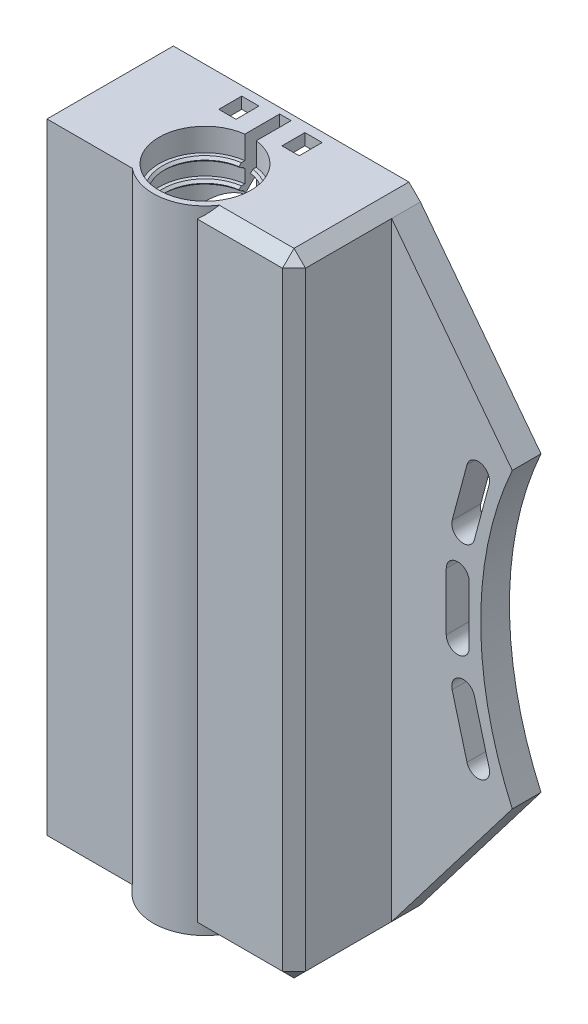
SolidWorks part; units mm, degrees
ref_plane "Alzado" through (0, 0, 0) normal (0, 0, 1) x (1, 0, 0)
ref_plane "Planta" through (0, 0, 0) normal (0, 1, 0) x (1, 0, 0)
ref_plane "Vista lateral" through (0, 0, 0) normal (1, 0, 0) x (0, 0, -1)
sketch "Croquis1" plane through (0, 0, 0) normal (0, 1, 0) x (1, 0, 0)
  line L1 (-5.6569, -7) -> (-22.5, -7)
  line L2 (-22.5, -7) -> (-22.5, 15)
  line L3 (-22.5, 15) -> (22.5, 15)
  line L4 (22.5, 15) -> (22.5, -7)
  line L5 (22.5, -7) -> (5.6569, -7)
  line L7 (0, 0) -> (0, 15696.111) construction
  line L8 (0, 0) -> (15696.111, 0) construction
  circle A0 centre (0, 0) radius 8
  arc A1 (-5.6569, -7) -> (5.6569, -7) centre (0, 0) ccw
  point P5 (0, 15)
  dimension "D1" = 16
  dimension "D2" = 9
  dimension "D3" = 45
  dimension "D4" = 22
  dimension "D5" = 15
extrude "Saliente-Extruir1" add sketch "Croquis1" along normal mid plane 110
sketch "Croquis3" plane through (0, 55, 0) normal (0, 1, 0) x (1, 0, 0)
  circle A0 centre (0, 0) radius 8
  circle A1 centre (0, 0) radius 7
  circle A2 centre (0, 0) radius 8 construction
  dimension "D1" = 1
extrude "Saliente-Extruir2" add sketch "Croquis3" against normal blind 0.8 from offset 4 offset against normal yes
pattern_linear "MatrizL1" count 2 spacing 3.5 along (0, -1, 0) of "Saliente-Extruir2"
mirror "Simetría1" about plane through (0, 0, 0) normal (0, 1, 0) of "MatrizL1"
chamfer "Chaflán3" distance 2 angle 45 9 edges at (-22.5, 55, -4) (-22.5, 0, 7) (-22.5, -55, -4) (-14.0784, -55, 7) (22.5, -55, -4) (22.5, 55, -4) (14.0784, -55, 7) (22.5, 0, 7) (14.0784, 55, 7)
shell "Vaciado1" thickness 2 removed face at (0, 0, -15)
sketch "Croquis6" plane through (0, 0, 0) normal (1, 0, 0) x (0, 0, -1)
  line L0 (15, 53) -> (-5, 33)
  line L1 (15, 53) -> (15, -53) construction
  line L3 (-5, 33) -> (-5, 0)
  line L4 (-5, 0) -> (15, 0)
  line L5 (15, 0) -> (15, 53)
  line L6 (15, 53) -> (-5, 53) construction
  line L7 (-5, 53) -> (-5, -53) construction
  dimension "D1" = 45
extrude "Cortar-Extruir4" cut sketch "Croquis6" against normal mid plane 25
mirror "Simetría2" about plane through (0, 0, 0) normal (0, 1, 0) of "Cortar-Extruir4"
chamfer "Chaflán1" distance 0.4 angle 45 8 edges at (0, 51, 7) (0, 50.2, 7) (0, 47.5, 7) (0, 46.7, 7) (0, -46.7, 7) (0, -47.5, 7) (0, -50.2, 7) (0, -51, 7)
chamfer "Chaflán2" distance 0.4 angle 45 4 edges at (0, 50.2, 8) (0, 46.7, 8) (0, -47.5, -8) (0, -51, -8)
sketch "Croquis4" plane through (0, 55, 0) normal (0, 1, 0) x (1, 0, 0)
  line L0 (0, 0) -> (0, 50000) construction
  line L2 (-1, 14) -> (1, 14)
  line L3 (-1, 14) -> (-1, 0)
  line L4 (-1, 0) -> (1, 0)
  line L5 (1, 14) -> (1, 0)
  line L6 (-1, 14) -> (1, 0) construction
  line L7 (-1, 0) -> (1, 14) construction
  line L9 (20.5, 15) -> (-20.5, 15) construction
  point P3 (0, 7)
  dimension "D1" = 2
  dimension "D2" = 1
extrude "Cortar-Extruir3" cut sketch "Croquis4" against normal through all
sketch "Croquis7" plane through (0, 55, 0) normal (0, 1, 0) x (1, 0, 0)
  line L0 (20.5, 15) -> (-20.5, 15) construction
  line L1 (-7, 13.4) -> (-4, 13.4)
  line L2 (-7, 13.4) -> (-7, 9.4)
  line L3 (-7, 9.4) -> (-4, 9.4)
  line L4 (-4, 13.4) -> (-4, 9.4)
  line L5 (-7, 13.4) -> (-4, 9.4) construction
  line L6 (-7, 9.4) -> (-4, 13.4) construction
  line L7 (-1, 14) -> (-1, 7.9373) construction
  point P4 (-5.5, 11.4)
  dimension "D1" = 3
  dimension "D2" = 4
  dimension "D3" = 1.6
  dimension "D4" = 3
extrude "Cortar-Extruir5" cut sketch "Croquis7" against normal through all
mirror "Simetría3" about plane through (0, 0, 0) normal (1, 0, 0) of "Cortar-Extruir5"
sketch "Croquis8" plane through (0, 0, -15) normal (0, 0, -1) x (-1, 0, 0)
  line L0 (0, 0) -> (-50000, 0) construction
  line L1 (-43.4962, 25.5211) -> (-22.5, 53)
  line L2 (-22.5, 53) -> (-22.5, -53)
  line L3 (-22.5, -53) -> (-43.4962, -25.5211)
  line L4 (-34, -5) -> (-34, 5) construction
  line L5 (-36, -5) -> (-36, 5)
  line L6 (-32, -5) -> (-32, 5)
  line L7 (-37.543, -21.9117) -> (-34.9548, -12.2524) construction
  line L8 (-39.4748, -21.394) -> (-36.8867, -11.7348)
  line L9 (-35.6111, -22.4293) -> (-33.0229, -12.7701)
  line L10 (-34.9548, 12.2524) -> (-37.543, 21.9117) construction
  line L11 (-36.8867, 11.7348) -> (-39.4748, 21.394)
  line L12 (-33.0229, 12.7701) -> (-35.6111, 22.4293)
  arc A0 (-43.4962, 25.5211) -> (-43.4962, -25.5211) centre (-100, 0) cw
  arc A1 (-39.4748, -21.394) -> (-35.6111, -22.4293) centre (-37.543, -21.9117) ccw
  arc A2 (-36, -5) -> (-32, -5) centre (-34, -5) ccw
  arc A3 (-32, 5) -> (-36, 5) centre (-34, 5) ccw
  arc A4 (-33.0229, -12.7701) -> (-36.8867, -11.7348) centre (-34.9548, -12.2524) ccw
  arc A5 (-36.8867, 11.7348) -> (-33.0229, 12.7701) centre (-34.9548, 12.2524) ccw
  arc A6 (-35.6111, 22.4293) -> (-39.4748, 21.394) centre (-37.543, 21.9117) ccw
  point P6 (-36.2489, -17.0821)
  point P9 (-34, 0)
  point P26 (-100, 0)
  point P28 (-36.2489, 17.0821)
  point P35 (-100, 0)
  dimension "D2" = 62
  dimension "D3" = 2
  dimension "D6" = 2
  dimension "D1" = 100
  dimension "D4" = 10
  dimension "D5" = 66
  dimension "D7" = 2
extrude "Saliente-Extruir3" add sketch "Croquis8" against normal blind 5
